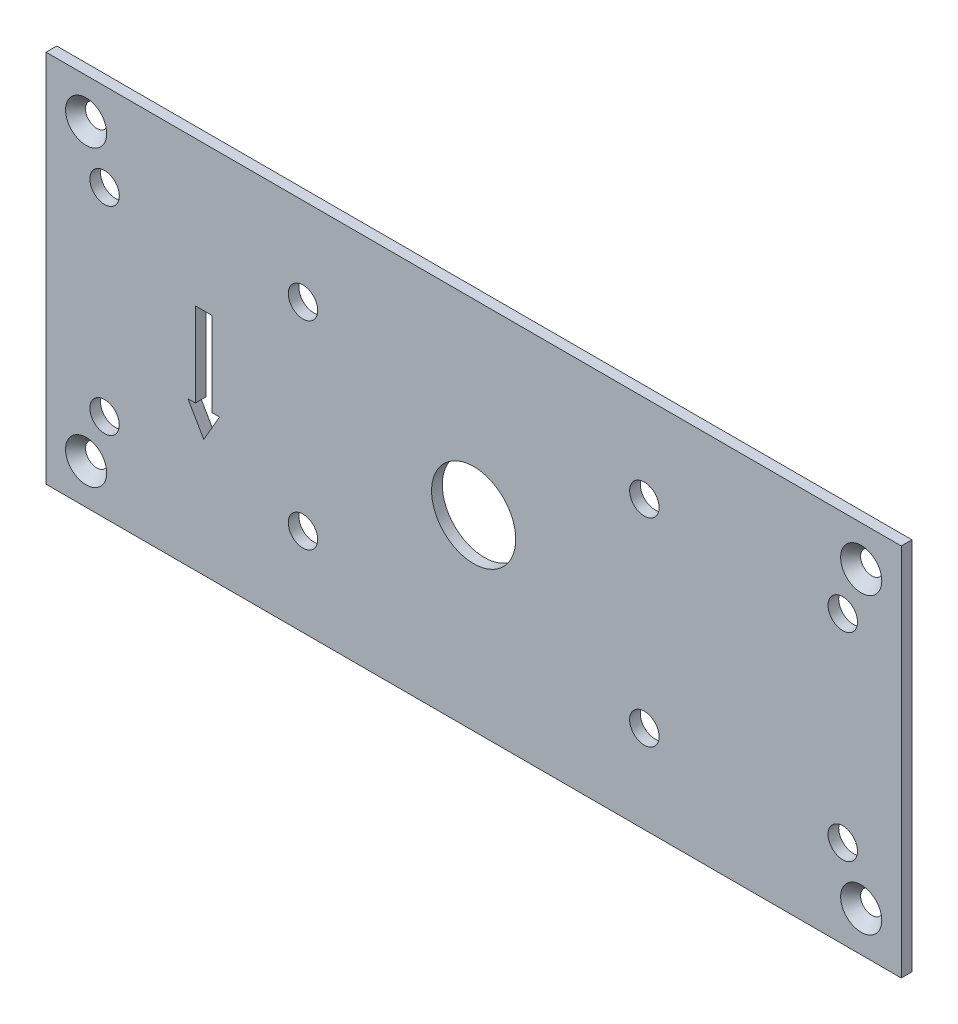
SolidWorks part; units mm, degrees
ref_plane "Front Plane" through (0, 0, 0) normal (0, 0, 1) x (1, 0, 0)
ref_plane "Top Plane" through (0, 0, 0) normal (0, 1, 0) x (1, 0, 0)
ref_plane "Right Plane" through (0, 0, 0) normal (1, 0, 0) x (0, 0, -1)
sketch "Sketch2" plane through (0, 0, 0) normal (0, 0, 1) x (1, 0, 0)
  line L0 (-40.555, 23.57) -> (-87.695, 23.57) construction
  line L1 (-101.6, -44.45) -> (101.6, -44.45)
  line L2 (-101.6, -44.45) -> (-101.6, 44.45)
  line L3 (-101.6, 44.45) -> (101.6, 44.45)
  line L4 (101.6, -44.45) -> (101.6, 44.45)
  line L5 (-101.6, -44.45) -> (101.6, 44.45) construction
  line L6 (-101.6, 44.45) -> (101.6, -44.45) construction
  line L7 (-87.695, 23.57) -> (-87.695, -23.57) construction
  line L8 (-87.695, -23.57) -> (-40.555, -23.57) construction
  line L9 (-40.555, -23.57) -> (-40.555, 23.57) construction
  line L10 (0, 0) -> (-64.125, 0) construction
  line L11 (0, 0) -> (64.125, 0) construction
  line L12 (40.555, -23.57) -> (87.695, -23.57) construction
  line L13 (87.695, -23.57) -> (87.695, 23.57) construction
  line L14 (87.695, 23.57) -> (40.555, 23.57) construction
  line L15 (40.555, 23.57) -> (40.555, -23.57) construction
  circle A11 centre (-87.695, 23.57) radius 3.5
  circle A12 centre (-40.555, 23.57) radius 3.5
  circle A13 centre (-40.555, -23.57) radius 3.5
  circle A14 centre (-87.695, -23.57) radius 3.5
  circle A15 centre (40.555, -23.57) radius 3.5
  circle A16 centre (87.695, -23.57) radius 3.5
  circle A17 centre (87.695, 23.57) radius 3.5
  circle A18 centre (40.555, 23.57) radius 3.5
  circle A19 centre (0, 0) radius 10
  point P0 (0, 0)
  point P28 (-64.125, 23.57)
  point P29 (64.125, 23.57)
  dimension "D3" = 7
  dimension "D6" = 20
  dimension "D1" = 47.14
  dimension "D2" = 88.9
  dimension "D4" = 203.2
  dimension "D5" = 64.125
extrude "Boss-Extrude1" add sketch "Sketch2" along normal mid plane 2.54
sketch "Sketch3" plane through (0, 0, 1.27) normal (0, 0, 1) x (1, 0, 0)
  line L0 (-101.6, 34.925) -> (-92.075, 34.925) construction
  line L1 (-101.6, 44.45) -> (-101.6, -44.45) construction
  line L2 (-92.075, 34.925) -> (-92.075, 44.45) construction
  line L3 (101.6, 44.45) -> (-101.6, 44.45) construction
  line L4 (92.075, 44.45) -> (92.075, 34.925) construction
  line L5 (92.075, 34.925) -> (101.6, 34.925) construction
  line L6 (101.6, -44.45) -> (101.6, 44.45) construction
  line L7 (92.075, -44.45) -> (92.075, -34.925) construction
  line L8 (-101.6, -44.45) -> (101.6, -44.45) construction
  line L9 (92.075, -34.925) -> (101.6, -34.925) construction
  line L10 (-92.075, -44.45) -> (-92.075, -34.925) construction
  line L11 (-92.075, -34.925) -> (-101.6, -34.925) construction
  circle A0 centre (-92.075, 34.925) radius 2.5527
  circle A1 centre (-92.075, -34.925) radius 2.5527
  circle A2 centre (92.075, -34.925) radius 2.5527
  circle A3 centre (92.075, 34.925) radius 2.5527
  dimension "D2" = 5.1054
  dimension "D1" = 9.525
extrude "Cut-Extrude1" cut sketch "Sketch3" against normal through all
sketch "Sketch4" plane through (0, 0, 1.27) normal (0, 0, 1) x (1, 0, 0)
  line L0 (-87.695, 23.57) -> (-40.555, -23.57) construction
  line L1 (-66.125, -10) -> (-67.8747, -10)
  line L2 (-66.125, -10) -> (-62.125, -10)
  line L3 (-66.125, -10) -> (-66.125, 10)
  line L4 (-66.125, 10) -> (-62.125, 10)
  line L5 (-62.125, -10) -> (-62.125, 10)
  line L6 (-66.125, -10) -> (-62.125, 10) construction
  line L7 (-66.125, 10) -> (-62.125, -10) construction
  line L8 (-67.8747, -10) -> (-64.125, -16.4946)
  line L9 (-64.125, -16.4946) -> (-60.3753, -10)
  line L10 (-62.125, -10) -> (-60.3753, -10)
  point P3 (-64.125, 0)
  dimension "D1" = 4
  dimension "D2" = 20
  dimension "D3" = 60
extrude "Cut-Extrude2" cut sketch "Sketch4" against normal through all both and the other way through all contours L10 L2 L1 L8 L9 | L2 L5 L4 L3 region at (-64.125, -12.1649, 1.27) region at (-64.125, 0, 1.27)
hole_wizard "CSK for #10 Oval Head Machine Screw1" positions "Sketch5" profile "Sketch6" countersink size "#10" standard "ANSI Inch" end condition through all
sketch "Sketch5" plane through (0, 0, 1.27) normal (0, 0, 1) x (1, 0, 0)
  point P0 (-92.075, 34.925)
  point P3 (-92.075, -34.925)
  point P6 (92.075, -34.925)
  point P9 (92.075, 34.925)
sketch "Sketch6" plane through (-92.075, 34.925, 1.27) normal (1, 0, 0) x (0, -1, 0)
  line L0 (0, 0) -> (0, 2.54)
  line L1 (0, 2.54) -> (2.5527, 2.54)
  line L2 (2.5527, 2.54) -> (2.5527, 2.6882)
  line L3 (2.5527, 2.6882) -> (4.8895, 0)
  line L5 (4.8895, 0) -> (0, 0)
  line L6 (-2.5527, 2.6882) -> (-4.8895, 0) construction
  line L11 (0, -6.35) -> (0, 107.95) construction
  dimension "Thru Hole Dia." = 5.1054
  dimension "Thru Hole Depth" = 2.54
  dimension "Near C'Sink Dia." = 9.779
  dimension "Near C'Sink Angle" = 82
